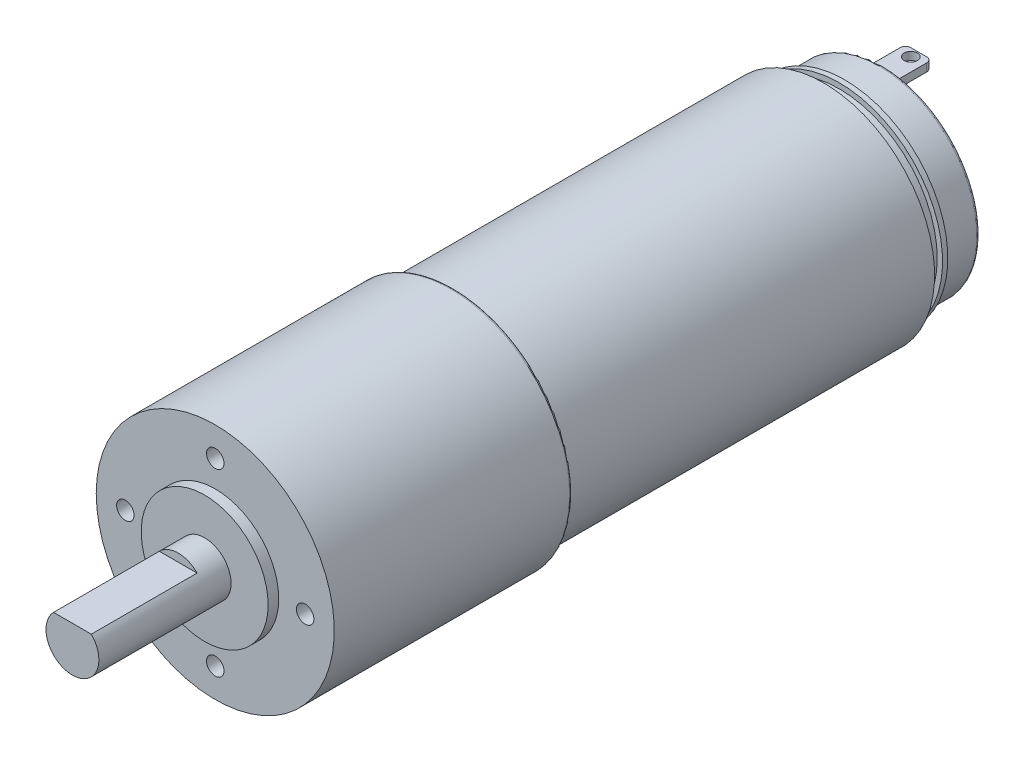
SolidWorks part; units mm, degrees
other "Markup1"
sketch "Sketch15" plane through (20, -20, 71) normal (0.3709, -0.3697, 0.8519) x (-0.8738, 0.1719, 0.455)
other "Markup2"
sketch "Sketch16" plane through (20, -20, 71) normal (0.3709, -0.3697, 0.8519) x (-0.8738, 0.1719, 0.455)
material "A286 Iron Base Superalloy"
ref_plane "Front Plane" through (0, 0, 0) normal (0, 0, 1) x (1, 0, 0)
ref_plane "Top Plane" through (0, 0, 0) normal (0, 1, 0) x (1, 0, 0)
ref_plane "Right Plane" through (0, 0, 0) normal (1, 0, 0) x (0, 0, -1)
sketch "Sketch2" plane through (0, 0, 0) normal (0, 0, 1) x (1, 0, 0)
  circle A0 centre (0, 0) radius 22.5
  dimension "D1" = 45
extrude "Boss-Extrude2" add sketch "Sketch2" along normal blind 45
sketch "Sketch3" plane through (0, 0, 45) normal (0, 0, 1) x (1, 0, 0)
  circle A0 centre (0, 0) radius 17 construction
  point P3 (0, 17)
  point P4 (-17, 0)
  point P5 (0, -17)
  point P6 (17, 0)
  dimension "D1" = 34
hole_wizard "M4 Tapped Hole2" positions "3DSketch2" profile "Sketch5" tap size "M4" standard "ISO"
sketch3d "3DSketch2"
  circle A0 centre (0, 0, 45) radius 17 construction
  point P0 (0, 17, 45)
  point P4 (0, 0, 62)
  point P5 (17, 0, 45)
  point P7 (0, -17, 45)
  point P9 (-17, 0, 45)
sketch "Sketch5" plane through (0, 17, 45) normal (1, 0, 0) x (0, -1, 0)
  line L0 (0, 0) -> (0, 11.0914)
  line L1 (0, 11.0914) -> (1.65, 10.1)
  line L2 (1.65, 10.1) -> (1.65, 0)
  line L5 (1.65, 0) -> (0, 0)
  line L10 (0, 11.0914) -> (-1.65, 10.1) construction
  line L11 (0, -6.35) -> (0, 107.95) construction
  dimension "Tap Drill Dia." = 3.3
  dimension "Tap Drill Depth" = 10.1
  dimension "Drill Angle" = 118
cosmetic thread "Hole Thread1" parameters "D1"=8, "D2"=4
cosmetic thread "Hole Thread2" parameters "D1"=8, "D2"=4
cosmetic thread "Hole Thread3" parameters "D1"=8, "D2"=4
cosmetic thread "Hole Thread4" parameters "D1"=8, "D2"=4
sketch "Sketch6" plane through (0, 0, 45) normal (0, 0, 1) x (1, 0, 0)
  circle A0 centre (0, 0) radius 12
  dimension "D1" = 24
extrude "Boss-Extrude3" add sketch "Sketch6" along normal blind 2
sketch "Sketch7" plane through (0, 0, 47) normal (0, 0, 1) x (1, 0, 0)
  circle A0 centre (0, 0) radius 5
  dimension "D1" = 10
extrude "Boss-Extrude4" add sketch "Sketch7" along normal blind 25
sketch "Sketch8" plane through (0, 0, 72) normal (0, 0, 1) x (1, 0, 0)
  line L0 (-3.5707, 3.5) -> (3.5707, 3.5)
  line L1 (0, 0) -> (5, 0) construction
  circle A1 centre (0, 0) radius 5
  arc A2 (3.5707, 3.5) -> (-3.5707, 3.5) centre (0, 0) ccw
  dimension "D2" = 3.5
  dimension "D1" = 0
extrude "Cut-Extrude1" cut sketch "Sketch8" against normal blind 20
sketch "Sketch9" plane through (0, 0, 0) normal (0, 0, -1) x (-1, 0, 0)
  circle A0 centre (0, 0) radius 21
  dimension "D1" = 42
extrude "Boss-Extrude5" add sketch "Sketch9" along normal blind 70
sketch "Sketch10" plane through (0, 0, -70) normal (0, 0, -1) x (-1, 0, 0)
  circle A0 centre (0, 0) radius 18.5
  dimension "D1" = 37
extrude "Boss-Extrude6" add sketch "Sketch10" along normal blind 3
sketch "Sketch11" plane through (0, 0, -73) normal (0, 0, -1) x (-1, 0, 0)
  circle A0 centre (0, 0) radius 19.5
  dimension "D1" = 39
extrude "Boss-Extrude7" add sketch "Sketch11" along normal blind 1
sketch "Sketch12" plane through (0, 0, -74) normal (0, 0, -1) x (-1, 0, 0)
  circle A0 centre (0, 0) radius 18.5
  dimension "D1" = 37
extrude "Boss-Extrude8" add sketch "Sketch12" along normal blind 7
sketch "Sketch13" plane through (0, 0, -81) normal (0, 0, -1) x (-1, 0, 0)
  line L0 (2.5, -17) -> (2.5, -15.5)
  line L1 (-2.5, 17) -> (2.5, 17)
  line L2 (-2.5, 17) -> (-2.5, 15.5)
  line L3 (-2.5, 15.5) -> (2.5, 15.5)
  line L4 (2.5, 17) -> (2.5, 15.5)
  line L5 (2.5, -17) -> (-2.5, -17)
  line L6 (-2.5, -17) -> (-2.5, -15.5)
  line L7 (2.5, -15.5) -> (-2.5, -15.5)
  point P4 (0, 15.5)
  dimension "D1" = 1.5
  dimension "D2" = 5
  dimension "D3" = 15.5
  dimension "D5" = 31
  dimension "D4" = 2
extrude "Boss-Extrude9" add sketch "Sketch13" along normal blind 7
sketch "Sketch14" plane through (0, -17, 0) normal (0, -1, 0) x (1, 0, 0)
  line L0 (2.5, -88) -> (-2.5, -88) construction
  circle A0 centre (0, -86.5) radius 1.25
  dimension "D1" = 2.5
  dimension "D2" = 1.5
extrude "Cut-Extrude2" cut sketch "Sketch14" against normal through all
fillet "Fillet1" radius 1 4 edges at (2.5, 16.25, -88) (-2.5, 16.25, -88) (2.5, -16.25, -88) (-2.5, -16.25, -88)
fillet "Fillet2" radius 0.5 1 edges at (-18.5, 0, -81)
fillet "Fillet3" radius 0.5 1 edges at (22.5, 0, 0)
